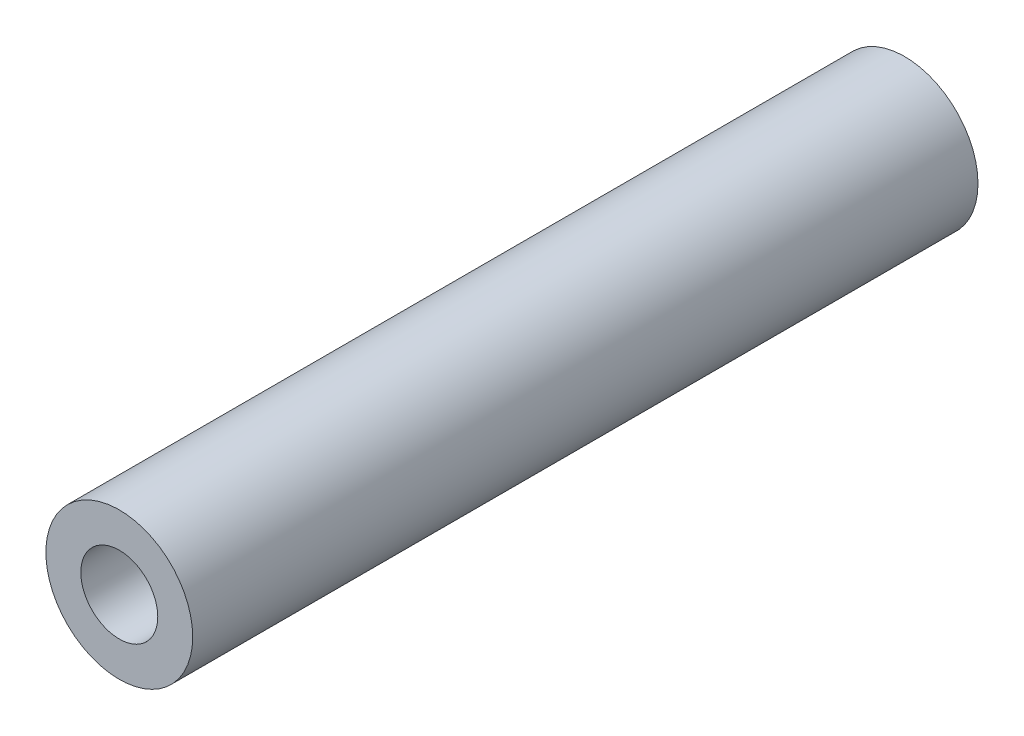
SolidWorks part; units mm, degrees
material "6061-T6 (SS)"
ref_plane "Front Plane" through (0, 0, 0) normal (0, 0, 1) x (1, 0, 0)
ref_plane "Top Plane" through (0, 0, 0) normal (0, 1, 0) x (1, 0, 0)
ref_plane "Right Plane" through (0, 0, 0) normal (1, 0, 0) x (0, 0, -1)
sketch "Sketch1" plane through (0, 0, 0) normal (0, 0, 1) x (1, 0, 0)
  circle A0 centre (0, 0) radius 4.7498
  circle A1 centre (0, 0) radius 2.4892
  dimension "D1" = 9.4996
  dimension "D2" = 4.9784
extrude "Boss-Extrude1" add sketch "Sketch1" along normal blind 50.8
